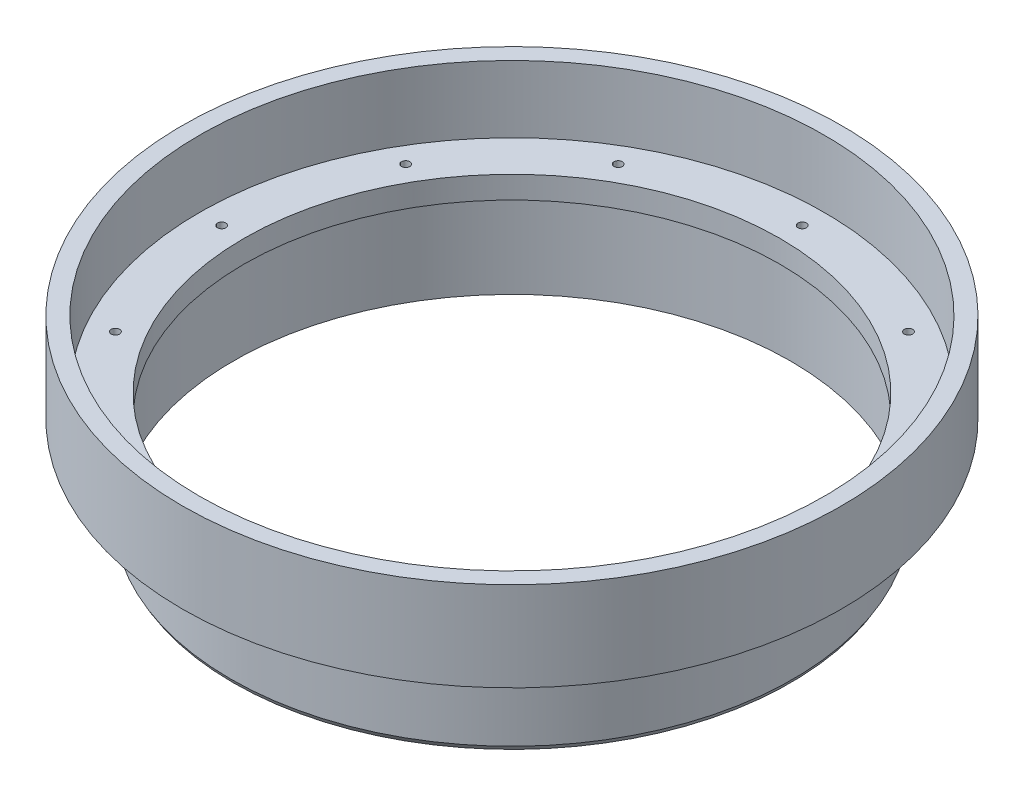
SolidWorks part; units mm, degrees
material "6061-T6 (SS)"
ref_plane "Front Plane" through (0, 0, 0) normal (0, 0, 1) x (1, 0, 0)
ref_plane "Top Plane" through (0, 0, 0) normal (0, 1, 0) x (1, 0, 0)
ref_plane "Right Plane" through (0, 0, 0) normal (1, 0, 0) x (0, 0, -1)
ref_axis "Axis1" through (0, 55, 0) along (0, -1, 0)
sketch "Cross Section" plane through (0, 0, 0) normal (0, 0, 1) x (1, 0, 0)
  line L0 (-38.1, 0) -> (-38.1, -3.175)
  line L1 (-38.1, -3.175) -> (-39.624, -3.175)
  line L2 (-39.624, -3.175) -> (-39.624, -15.875)
  line L3 (-39.624, -15.875) -> (-40.005, -15.2151)
  line L4 (0, -15.875) -> (-38.1, -15.875) construction
  line L5 (-40.005, -15.2151) -> (-40.005, -3.175)
  line L6 (-40.005, -3.175) -> (-46.863, -3.175)
  line L7 (-46.863, -3.175) -> (-46.863, 9.525)
  line L8 (-46.863, 9.525) -> (-44.45, 9.525)
  line L9 (-44.45, 9.525) -> (-44.45, 0)
  line L10 (-44.45, 0) -> (-38.1, 0)
  line L11 (-38.1, 0) -> (0, 0) construction
  line L12 (0, 55) -> (0, -55) construction
  line L14 (-44.45, 1.5875) -> (-44.45, 3.175) construction
  dimension "D1" = 1.524
  dimension "D3" = 0.381
  dimension "D4" = 30
  dimension "D5" = 6.858
  dimension "D6" = 12.7
  dimension "D9" = 3.175
  dimension "D8" = 38.1
revolve "Main" add sketch "Cross Section" angle 360 about axis through (0, 55, 0) along (0, -1, 0)
sketch "Hole Location" plane through (0, 0, 0) normal (0, 1, 0) x (1, 0, 0)
  line L0 (0, 0) -> (-41.275, 0) construction
  circle A0 centre (0, 0) radius 41.275 construction
  dimension "D1" = 82.55
hole_wizard "#0-80 Tapped Hole1" positions "Sketch5" profile "Sketch7" tap size "#0-80" standard "ANSI Inch"
sketch "Sketch5" plane through (0, 0, 0) normal (0, 1, 0) x (1, 0, 0)
  point P0 (-41.275, 0)
sketch "Sketch7" plane through (-41.275, 0, 0) normal (1, 0, 0) x (0, 0, 1)
  line L0 (0, 0) -> (0, 3.5329)
  line L1 (0, 3.5329) -> (0.5956, 3.175)
  line L2 (0.5956, 3.175) -> (0.5956, 0)
  line L5 (0.5956, 0) -> (0, 0)
  line L10 (0, 3.5329) -> (-0.5956, 3.175) construction
  line L11 (0, -6.35) -> (0, 107.95) construction
  dimension "Tap Drill Dia." = 1.1913
  dimension "Tap Drill Depth" = 3.175
  dimension "Drill Angle" = 118
cosmetic thread "Hole Thread1" parameters "D1"=3.048, "D2"=1.524
pattern_circular "Screw Holes" count 12 over 360 about axis through (0, 55, 0) along (0, -1, 0) of "#0-80 Tapped Hole1"
equation "\"D8@Cross Section\"=\"TANK DIAMETER@Cryo Tank.Assembly\"/2"
equation "\"D1@Hole Location\"=\"TANK DIAMETER@Cryo Tank.Assembly\"+\"GASKET SEAT THICKNESS@Cryo Tank.Assembly\""
equation "\"D1@Cross Section\"=\"LINER THICKNESS@Cryo Tank.Assembly\""
equation "\"D3@Cross Section\"=\"ALUMINUM LAP THICKNESS@Cryo Tank.Assembly\""
equation "\"D5@Cross Section\"=2*\"CF THICKNESS@Cryo Tank.Assembly\"+\"NOMEX THICKNESS@Cryo Tank.Assembly\""
